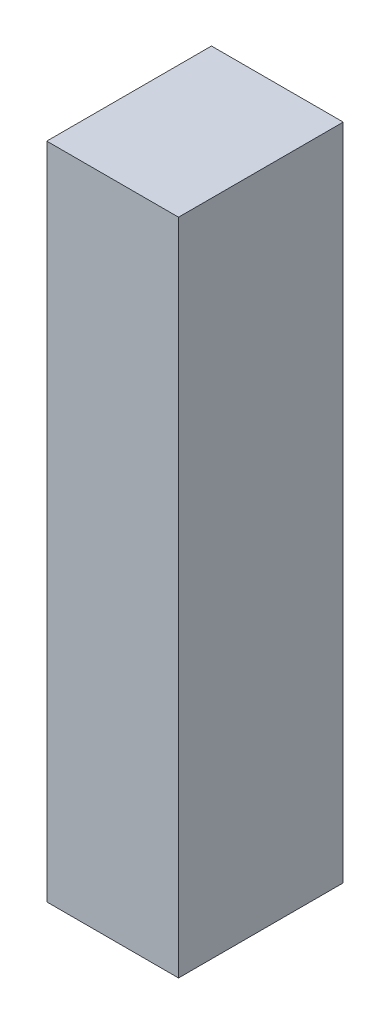
SolidWorks part; units mm, degrees
ref_plane "Front Plane" through (0, 0, 0) normal (0, 0, 1) x (1, 0, 0)
ref_plane "Top Plane" through (0, 0, 0) normal (0, 1, 0) x (1, 0, 0)
ref_plane "Right Plane" through (0, 0, 0) normal (1, 0, 0) x (0, 0, -1)
sketch "Sketch1" plane through (0, 0, 0) normal (0, 1, 0) x (1, 0, 0)
  line L1 (-6, 7.5) -> (6, 7.5)
  line L2 (-6, 7.5) -> (-6, -7.5)
  line L3 (-6, -7.5) -> (6, -7.5)
  line L4 (6, 7.5) -> (6, -7.5)
  line L5 (-6, 7.5) -> (6, -7.5) construction
  line L6 (-6, -7.5) -> (6, 7.5) construction
  point P0 (0, 0)
  dimension "D1" = 12
  dimension "D2" = 15
extrude "Boss-Extrude1" add sketch "Sketch1" along normal blind 10 and the other way blind 50
